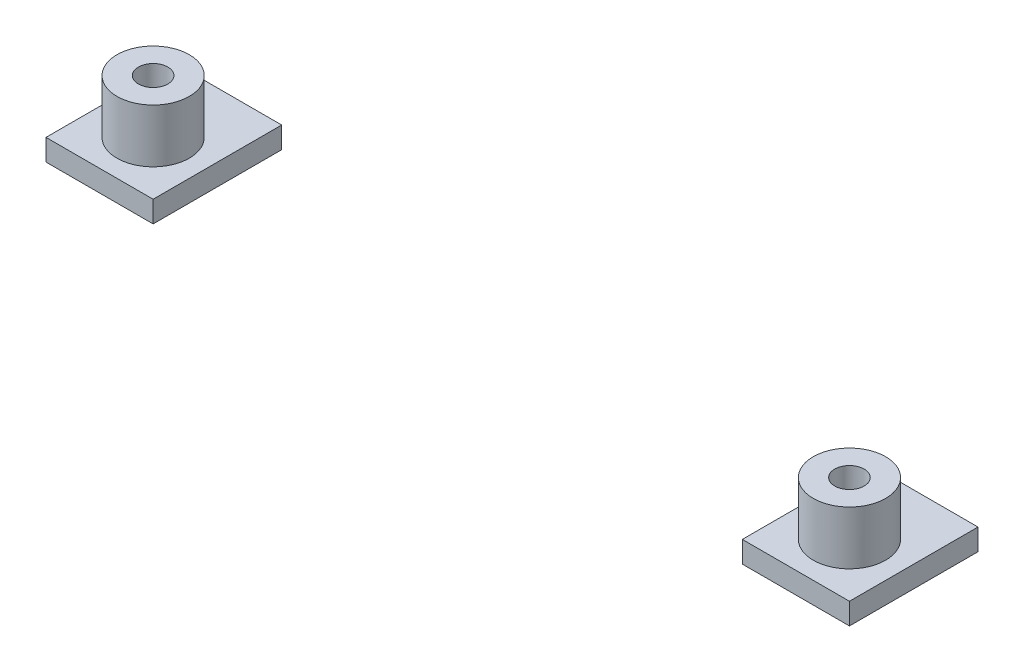
SolidWorks part; units mm, degrees
material "1060 Alloy"
ref_plane "Front Plane" through (0, 0, 0) normal (0, 0, 1) x (1, 0, 0)
ref_plane "Top Plane" through (0, 0, 0) normal (0, 1, 0) x (1, 0, 0)
ref_plane "Right Plane" through (0, 0, 0) normal (1, 0, 0) x (0, 0, -1)
sketch "Sketch1" plane through (0, 0, 0) normal (0, 0, 1) x (1, 0, 0)
  line L0 (-37.5, 0) -> (37.5, 0)
  line L1 (37.5, 2) -> (37.5, 0)
  line L2 (-37.5, 11) -> (-37.5, -4) construction
  line L3 (-37.5, 2) -> (-37.5, 0)
  line L5 (37.5, 2) -> (-37.5, 2)
  line L6 (0, 0) -> (0, 2) construction
  dimension "D1" = 2
extrude "Boss-Extrude1" add sketch "Sketch1" along normal up to surface (10 mm away)
sketch "Sketch2" plane through (0, 2, 0) normal (0, 1, 0) x (1, 0, 0)
  line L0 (0, 0) -> (0, -10) construction
  line L1 (37.5, -10) -> (37.5, 0) construction
  line L2 (32.5, -5) -> (32.5, -10) construction
  line L3 (37.5, -10) -> (-37.5, -10) construction
  line L5 (32.5, -5) -> (37.5, -5) construction
  line L6 (0, -10) -> (37.5, -10) construction
  line L7 (37.5, -10) -> (37.5, 0) construction
  line L8 (37.5, 0) -> (0, 0) construction
  circle A0 centre (32.5, -5) radius 1.375
  circle A1 centre (32.5, -5) radius 3.375
  circle A2 centre (18.75, -5) radius 1.375 construction
  circle A3 centre (-32.5, -5) radius 1.375
  circle A4 centre (-32.5, -5) radius 3.375
  dimension "D1" = 2
extrude "Boss-Extrude2" add sketch "Sketch2" along normal blind 5
sketch "Sketch3" plane through (0, 2, 0) normal (0, 1, 0) x (1, 0, 0)
  circle A0 centre (32.5, -5) radius 1.375
  circle A1 centre (-32.5, -5) radius 1.375
  circle A2 centre (32.5, -5) radius 1.375 construction
  circle A3 centre (-32.5, -5) radius 1.375 construction
extrude "Cut-Extrude1" cut sketch "Sketch3" against normal through all
sketch "Sketch4" plane through (0, 2, 0) normal (0, 1, 0) x (1, 0, 0)
  line L0 (0, -10) -> (0, 0) construction
  line L1 (37.5, -10) -> (-37.5, -10) construction
  line L2 (37.5, 0) -> (-37.5, 0) construction
  line L3 (32.5, -5) -> (32.5, -10) construction
  line L4 (-27.5, 0) -> (27.5, 0)
  line L5 (-27.5, 0) -> (-27.5, -10)
  line L6 (-27.5, -10) -> (27.5, -10)
  line L7 (27.5, 0) -> (27.5, -10)
  line L8 (-27.5, 0) -> (27.5, -10) construction
  line L9 (-27.5, -10) -> (27.5, 0) construction
  line L10 (32.5, -5) -> (37.5, -5) construction
  line L11 (37.5, -10) -> (37.5, 0) construction
  line L12 (32.5, -5) -> (27.5, -5) construction
  point P6 (0, -5)
extrude "Cut-Extrude2" cut sketch "Sketch4" against normal blind 10
sketch "Sketch5" plane through (0, 0, 0) normal (0, 0, -1) x (-1, 0, 0)
  line L4 (-37.5, 0) -> (-27.5, 0)
  line L5 (-27.5, 0) -> (-27.5, 2)
  line L6 (-27.5, 2) -> (-37.5, 2)
  line L7 (-37.5, 2) -> (-37.5, 0)
  line L8 (-37.5, 0) -> (-27.5, 0)
  line L9 (-27.5, 0) -> (-27.5, 2)
  line L10 (-27.5, 2) -> (-37.5, 2)
  line L11 (-37.5, 2) -> (-37.5, 0)
  dimension "D1" = 0
extrude "Boss-Extrude3" add sketch "Sketch5" along normal blind 2
sketch "Sketch6" plane through (0, 0, 0) normal (0, 0, -1) x (-1, 0, 0)
  line L4 (37.5, 2) -> (27.5, 2)
  line L5 (27.5, 2) -> (27.5, 0)
  line L6 (27.5, 0) -> (37.5, 0)
  line L7 (37.5, 0) -> (37.5, 2)
  line L8 (37.5, 2) -> (27.5, 2)
  line L9 (27.5, 2) -> (27.5, 0)
  line L10 (27.5, 0) -> (37.5, 0)
  line L11 (37.5, 0) -> (37.5, 2)
  dimension "D1" = 0
extrude "Boss-Extrude4" add sketch "Sketch6" along normal blind 2
